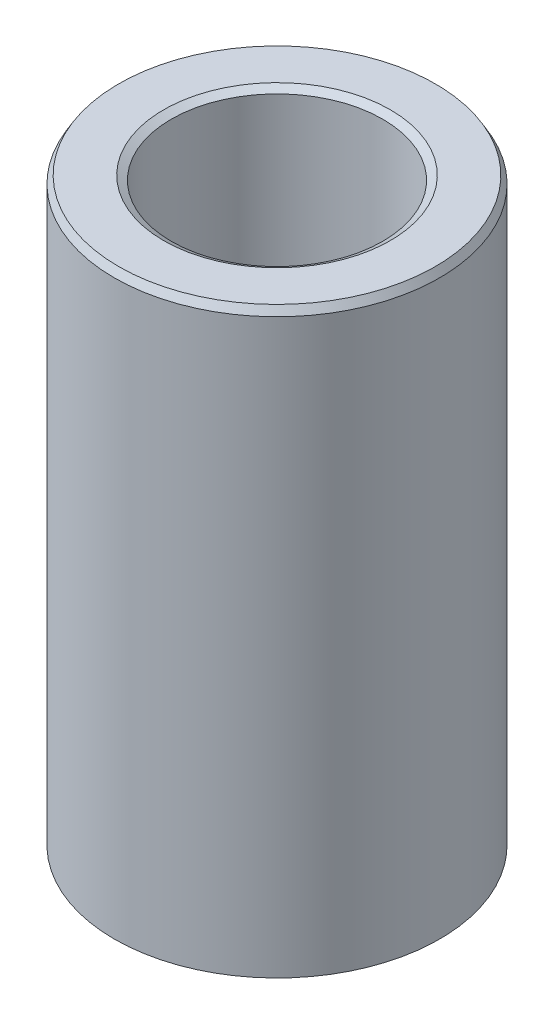
SolidWorks part; units mm, degrees
ref_plane "Front Plane" through (0, 0, 0) normal (0, 0, 1) x (1, 0, 0)
ref_plane "Top Plane" through (0, 0, 0) normal (0, 1, 0) x (1, 0, 0)
ref_plane "Right Plane" through (0, 0, 0) normal (1, 0, 0) x (0, 0, -1)
sketch "Sketch1" plane through (0, 0, 0) normal (0, 1, 0) x (1, 0, 0)
  circle A0 centre (0, 0) radius 50
  dimension "SLEEVE_OD" = 100
extrude "Boss-Extrude1" add sketch "Sketch1" along normal blind 179.6837
sketch "Sketch2" plane through (0, 0, 0) normal (0, 1, 0) x (1, 0, 0)
  circle A0 centre (0, 0) radius 32.5134
  dimension "BORE_D" = 65.0267
extrude "Cut-Extrude1" cut sketch "Sketch2" along normal through all
chamfer "Chamfer1" distance 2.329 angle 30 4 edges at (0, 179.6837, 32.5134) (0, 0, 32.5134) (0, 0, 50) (0, 179.6837, 50) first distance on face at (0, 179.6837, 32.5134) first distance on face at (0, 0, 32.5134) first distance on face at (0, 179.6837, 50)
